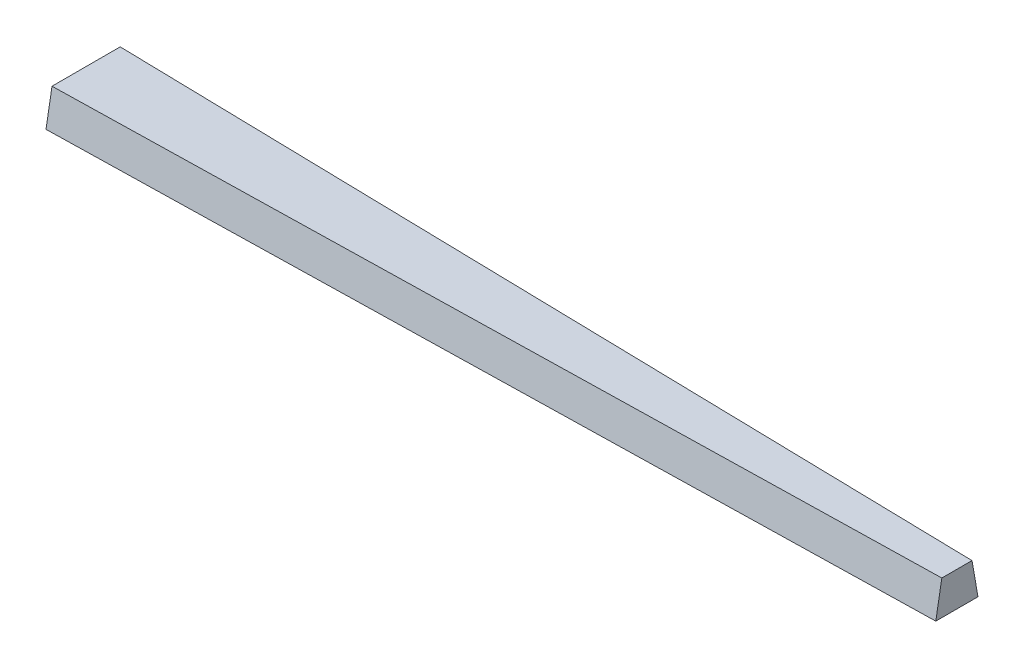
SolidWorks part; units mm, degrees
ref_plane "Front Plane" through (0, 0, 0) normal (0, 0, 1) x (1, 0, 0)
ref_plane "Top Plane" through (0, 0, 0) normal (0, 1, 0) x (1, 0, 0)
ref_plane "Right Plane" through (0, 0, 0) normal (1, 0, 0) x (0, 0, -1)
sketch "Sketch1" plane through (0, 0, 0) normal (0, 1, 0) x (1, 0, 0)
  line L0 (0, 0) -> (3.7897, 0) construction
  line L1 (0, 0) -> (482.6, 0) construction
  line L2 (0, -22.225) -> (0, 22.225)
  line L3 (0, 22.225) -> (482.6, 11.6946)
  line L4 (482.6, 11.6946) -> (482.6, -11.6946)
  line L5 (0, -22.225) -> (482.6, -11.6946)
  dimension "D1" = 482.6
  dimension "D2" = 1.25
  dimension "D3" = 44.45
extrude "Boss-Extrude1" add sketch "Sketch1" along normal blind 19.05
chamfer "Chamfer1" distance 19.05 angle 9.93 2 edges at (241.3, 19.05, 16.9598) (241.3, 19.05, -16.9598) first distance on face at (241.3, 9.525, 16.9598) first distance on face at (241.3, 9.525, -16.9598)
sketch "Sketch2" plane through (0, 0, 0) normal (0, 0, 1) x (1, 0, 0)
  line L0 (0, 127) -> (482.6, 66.675) construction
  line L1 (482.6, 66.675) -> (482.6, 19.05) construction
  line L2 (0, 127) -> (0, 19.05) construction
  dimension "D1" = 107.95
  dimension "D2" = 47.625
